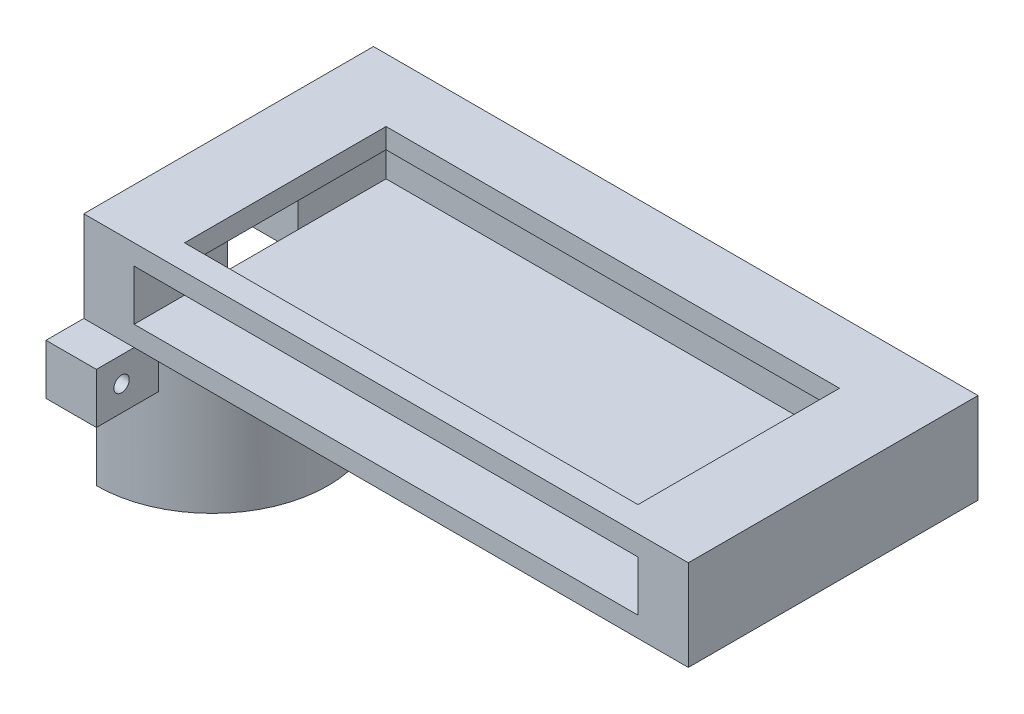
SolidWorks part; units mm, degrees
ref_plane "Front Plane" through (0, 0, 0) normal (0, 0, 1) x (1, 0, 0)
ref_plane "Top Plane" through (0, 0, 0) normal (0, 1, 0) x (1, 0, 0)
ref_plane "Right Plane" through (0, 0, 0) normal (1, 0, 0) x (0, 0, -1)
sketch "Sketch5" plane through (0, 0, 0) normal (0, 1, 0) x (1, 0, 0)
  line L1 (0, 0) -> (-120, 0)
  line L2 (0, 0) -> (0, 57.5)
  line L3 (0, 57.5) -> (-120, 57.5)
  line L4 (-120, 0) -> (-120, 57.5)
  line L5 (-10, 0) -> (-110, 0)
  line L6 (-10, 0) -> (-10, 50)
  line L7 (-10, 50) -> (-110, 50)
  line L8 (-110, 0) -> (-110, 50)
  dimension "D1" = 57.5
  dimension "D2" = 120
  dimension "D3" = 100
  dimension "D4" = 50
  dimension "D5" = 10
extrude "Main Body" add sketch "Sketch5" against normal blind 14 contours L1 L8 L7 L6 L2 L3 L4 region at (-5, 0, -1.3306)
sketch "Sketch6" plane through (0, 0, 0) normal (0, 1, 0) x (1, 0, 0)
  line L1 (-10, 50) -> (-110, 50)
  line L2 (-10, 50) -> (-10, 0)
  line L3 (-10, 0) -> (-110, 0)
  line L4 (-110, 50) -> (-110, 0)
extrude "Rail" add sketch "Sketch6" against normal blind 4
sketch "Sketch7" plane through (0, -4, 0) normal (0, -1, 0) x (1, 0, 0)
  line L0 (-110, -50) -> (-110, 0) construction
  line L1 (-15, -45) -> (-105, -45)
  line L2 (-15, -45) -> (-15, -5)
  line L3 (-15, -5) -> (-105, -5)
  line L4 (-105, -45) -> (-105, -5)
  line L5 (-10, -50) -> (-110, -50) construction
  line L6 (-10, 0) -> (-10, -50) construction
  line L7 (-110, 0) -> (-10, 0) construction
  dimension "D1" = 5
  dimension "D2" = 5
  dimension "D3" = 5
  dimension "D4" = 5
extrude "Window" cut sketch "Sketch7" against normal through all
sketch "Sketch8" plane through (0, 0, 0) normal (0, 0, 1) x (1, 0, 0)
  line L1 (0, -14) -> (-120, -14)
  line L2 (0, -14) -> (0, -18)
  line L3 (0, -18) -> (-120, -18)
  line L4 (-120, -14) -> (-120, -18)
  dimension "D1" = 4
extrude "Cover" add sketch "Sketch8" against normal up to surface (57.5 mm away) up to face at (-60, -7, -57.5)
sketch "Sketch9" plane through (-120, 0, 0) normal (-1, 0, 0) x (0, 0, 1)
  line L0 (-57.5, -18) -> (0, -18) construction
  line L1 (-18.5, -18) -> (-32.5, -18)
  line L2 (-18.5, -18) -> (-18.5, -4)
  line L3 (-18.5, -4) -> (-32.5, -4)
  line L4 (-32.5, -18) -> (-32.5, -4)
  line L5 (-57.5, -18) -> (-57.5, 0) construction
  line L6 (0, -18) -> (0, 0) construction
  dimension "D1" = 14
  dimension "D2" = 14
  dimension "D3" = 25
extrude "SiPM Window" cut sketch "Sketch9" against normal up to surface (10 mm away) up to face at (-110, -9, -25)
sketch "Sketch10" plane through (0, -18, 0) normal (0, -1, 0) x (1, 0, 0)
  line L0 (-120, -57.5) -> (-120, -32.5) construction
  line L4 (-120, -18.5) -> (-120, 0) construction
  line L5 (-120, -57.5) -> (0, -57.5) construction
  line L6 (-120, -5.5) -> (-120, -2.5)
  line L7 (-120, -45.5) -> (-120, -48.5)
  arc A0 (-120, -45.5) -> (-120, -5.5) centre (-120, -25.5) ccw
  arc A1 (-120, -48.5) -> (-120, -2.5) centre (-120, -25.5) ccw
  point P5 (-100, -25.5)
  line M4 (-120, -32.5) -> (-120, -57.5)
  line M8 (-120, 0) -> (-120, -18.5)
  dimension "D2" = 20
  dimension "D1" = 32
  dimension "D3" = 3
  dimension "D4" = 3
extrude "Tube Adapter" add sketch "Sketch10" along normal blind 30 contours A1 A0 M4 M8 region at (-119.4857, -18, -4)
sketch "Sketch11" plane through (0, -18, 0) normal (0, -1, 0) x (1, 0, 0)
  line L1 (-120, -57.5) -> (-110, -57.5)
  line L2 (-120, -57.5) -> (-120, -48.5)
  line L4 (-110, -57.5) -> (-110, -46.2123)
  arc A0 (-120, -48.5) -> (-110, -46.2123) centre (-120, -25.5) ccw
  dimension "D1" = 10
extrude "Right Screw Terminal" add sketch "Sketch11" along normal blind 10
sketch "Sketch12" plane through (-120, 0, 0) normal (-1, 0, 0) x (0, 0, 1)
  line L0 (-48.5, -28) -> (-57.5, -28) construction
  line L1 (-57.5, -28) -> (-57.5, 0) construction
  circle A0 centre (-52.5, -23) radius 1.524
  dimension "D3" = 3.048
  dimension "D1" = 5
  dimension "D2" = 5
extrude "Right Screw Hole" cut sketch "Sketch12" against normal up to next
sketch "Sketch13" plane through (0, -18, 0) normal (0, -1, 0) x (-1, 0, 0)
  line L2 (120, 2.5) -> (120, -7.5)
  line L3 (120, -7.5) -> (110, -7.5)
  line L4 (110, 4.7877) -> (110, -7.5)
  arc A0 (120, 2.5) -> (110, 4.7877) centre (120, 25.5) cw
  dimension "D1" = 10
  dimension "D2" = 10
extrude "Left Screw Terminal" add sketch "Sketch13" along normal blind 10
sketch "Sketch14" plane through (-120, 0, 0) normal (-1, 0, 0) x (0, 0, 1)
  line L0 (7.5, -28) -> (7.5, -18) construction
  line L1 (7.5, -28) -> (-2.5, -28) construction
  circle A0 centre (2.5, -23) radius 1.524
  dimension "D3" = 3.048
  dimension "D1" = 5
  dimension "D2" = 5
extrude "Left Screw Hole" cut sketch "Sketch14" against normal up to next
